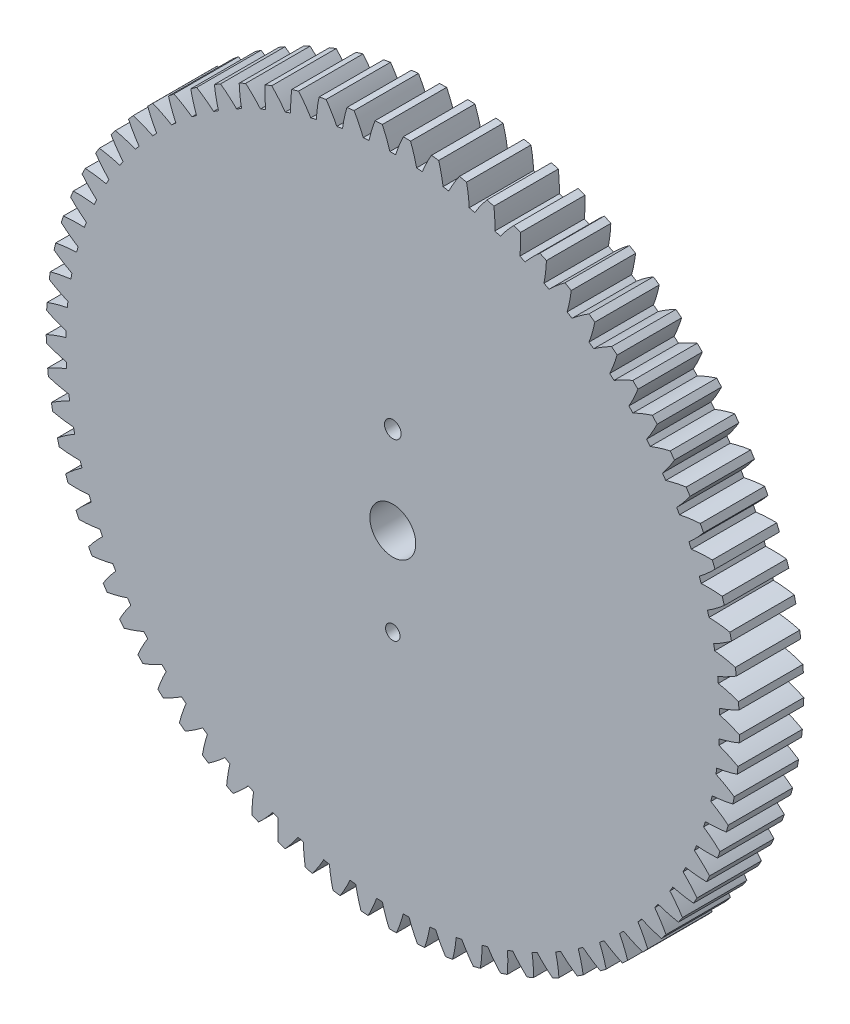
SolidWorks part; units mm, degrees
ref_plane "Front Plane" through (0, 0, 0) normal (0, 0, 1) x (1, 0, 0)
ref_plane "Top Plane" through (0, 0, 0) normal (0, 1, 0) x (1, 0, 0)
ref_plane "Right Plane" through (0, 0, 0) normal (1, 0, 0) x (0, 0, -1)
sketch "Model" plane through (0, 0, 0) normal (0, 0, 1) x (1, 0, 0)
  arc A0 (-39.5739, 2.0126) -> (-37.3581, 1.0914) centre (-32.524, 15.8446) ccw
  arc A1 (-37.3581, 1.0914) -> (-37.3715, 0.4333) centre (0, 0) ccw
  arc A2 (-37.3715, 0.4333) -> (-39.623, -0.3968) centre (-33.1432, -14.5048) ccw
  circle A311 centre (0, -10.05) radius 0.825
  circle A312 centre (0, 10.05) radius 0.825
  circle A313 centre (0, 0) radius 2.625
  arc A314 (-39.623, -0.3968) -> (-39.6062, -1.2197) centre (0, 0) ccw
  arc A315 (-39.6062, -1.2197) -> (-37.3227, -1.9572) centre (-33.7072, 13.1409) ccw
  arc A316 (-37.3227, -1.9572) -> (-37.2825, -2.6143) centre (0, 0) ccw
  arc A317 (-37.2825, -2.6143) -> (-39.4588, -3.6251) centre (-31.8506, -17.158) ccw
  arc A318 (-39.4588, -3.6251) -> (-39.375, -4.4439) centre (0, 0) ccw
  arc A319 (-39.375, -4.4439) -> (-37.039, -4.9929) centre (-34.6662, 10.3497) ccw
  arc A320 (-37.039, -4.9929) -> (-36.9453, -5.6445) centre (0, 0) ccw
  arc A321 (-36.9453, -5.6445) -> (-39.0321, -6.8293) centre (-30.3461, -19.6971) ccw
  arc A322 (-39.0321, -6.8293) -> (-38.8818, -7.6386) centre (0, 0) ccw
  arc A323 (-38.8818, -7.6386) -> (-36.5088, -7.9953) centre (-35.3944, 7.4897) ccw
  arc A324 (-36.5088, -7.9953) -> (-36.3623, -8.6371) centre (0, 0) ccw
  arc A325 (-36.3623, -8.6371) -> (-38.3455, -9.988) centre (-28.6396, -22.105) ccw
  arc A326 (-38.3455, -9.988) -> (-38.1298, -10.7824) centre (0, 0) ccw
  arc A327 (-38.1298, -10.7824) -> (-35.7356, -10.9445) centre (-35.8871, 4.5798) ccw
  arc A328 (-35.7356, -10.9445) -> (-35.5373, -11.5722) centre (0, 0) ccw
  arc A329 (-35.5373, -11.5722) -> (-37.4038, -13.0803) centre (-26.7426, -24.3659) ccw
  arc A330 (-37.4038, -13.0803) -> (-37.124, -13.8544) centre (0, 0) ccw
  arc A331 (-37.124, -13.8544) -> (-34.7246, -13.8209) centre (-36.141, 1.6394) ccw
  arc A332 (-34.7246, -13.8209) -> (-34.4758, -14.4303) centre (0, 0) ccw
  arc A333 (-34.4758, -14.4303) -> (-36.2132, -16.0856) centre (-24.6675, -26.4646) ccw
  arc A334 (-36.2132, -16.0856) -> (-35.8713, -16.8343) centre (0, 0) ccw
  arc A335 (-35.8713, -16.8343) -> (-33.4826, -16.6052) centre (-36.1544, -1.3119) ccw
  arc A336 (-33.4826, -16.6052) -> (-33.1849, -17.1924) centre (0, 0) ccw
  arc A337 (-33.1849, -17.1924) -> (-34.7816, -18.9838) centre (-22.4283, -28.3871) ccw
  arc A338 (-34.7816, -18.9838) -> (-34.3797, -19.7021) centre (0, 0) ccw
  arc A339 (-34.3797, -19.7021) -> (-32.0177, -19.2791) centre (-35.9271, -4.2544) ccw
  arc A340 (-32.0177, -19.2791) -> (-31.6731, -19.8401) centre (0, 0) ccw
  arc A341 (-31.6731, -19.8401) -> (-33.1185, -21.7556) centre (-20.0399, -30.1208) ccw
  arc A342 (-33.1185, -21.7556) -> (-32.6594, -22.4388) centre (0, 0) ccw
  arc A343 (-32.6594, -22.4388) -> (-30.3397, -21.8247) centre (-35.4608, -7.1687) ccw
  arc A344 (-30.3397, -21.8247) -> (-29.9506, -22.3557) centre (0, 0) ccw
  arc A345 (-29.9506, -22.3557) -> (-31.235, -24.3827) centre (-17.5181, -31.654) ccw
  arc A346 (-31.235, -24.3827) -> (-30.7218, -25.0262) centre (0, 0) ccw
  arc A347 (-30.7218, -25.0262) -> (-28.4598, -24.2251) centre (-34.7585, -10.0352) ccw
  arc A348 (-28.4598, -24.2251) -> (-28.0287, -24.7226) centre (0, 0) ccw
  arc A349 (-28.0287, -24.7226) -> (-29.1437, -26.8475) centre (-14.8797, -32.9766) ccw
  arc A350 (-29.1437, -26.8475) -> (-28.5797, -27.4471) centre (0, 0) ccw
  arc A351 (-28.5797, -27.4471) -> (-26.3906, -26.4642) centre (-33.8249, -12.835) ccw
  arc A352 (-26.3906, -26.4642) -> (-25.9204, -26.9249) centre (0, 0) ccw
  arc A353 (-25.9204, -26.9249) -> (-26.8584, -29.1336) centre (-12.1423, -34.0797) ccw
  arc A354 (-26.8584, -29.1336) -> (-26.2474, -29.6852) centre (0, 0) ccw
  arc A355 (-26.2474, -29.6852) -> (-24.1457, -28.5272) centre (-32.6662, -15.5493) ccw
  arc A356 (-24.1457, -28.5272) -> (-23.6395, -28.9481) centre (0, 0) ccw
  arc A357 (-23.6395, -28.9481) -> (-24.3943, -31.2259) centre (-9.3241, -34.956) ccw
  arc A358 (-24.3943, -31.2259) -> (-23.7405, -31.7259) centre (0, 0) ccw
  arc A359 (-23.7405, -31.7259) -> (-21.7401, -30.4004) centre (-31.2901, -18.1602) ccw
  arc A360 (-21.7401, -30.4004) -> (-21.2013, -30.7786) centre (0, 0) ccw
  arc A361 (-21.2013, -30.7786) -> (-21.768, -33.1104) centre (-6.4438, -35.5997) ccw
  arc A362 (-21.768, -33.1104) -> (-21.0755, -33.5554) centre (0, 0) ccw
  arc A363 (-21.0755, -33.5554) -> (-19.1898, -32.0713) centre (-29.7057, -20.6502) ccw
  arc A364 (-19.1898, -32.0713) -> (-18.622, -32.4043) centre (0, 0) ccw
  arc A365 (-18.622, -32.4043) -> (-18.9967, -34.7745) centre (-3.5207, -36.0065) ccw
  arc A366 (-18.9967, -34.7745) -> (-18.2703, -35.1616) centre (0, 0) ccw
  arc A367 (-18.2703, -35.1616) -> (-16.5119, -33.5287) centre (-27.9237, -23.0027) ccw
  arc A368 (-16.5119, -33.5287) -> (-15.9188, -33.8143) centre (0, 0) ccw
  arc A369 (-15.9188, -33.8143) -> (-16.0991, -36.2072) centre (-0.5741, -36.1736) ccw
  arc A370 (-16.0991, -36.2072) -> (-15.3435, -36.5338) centre (0, 0) ccw
  arc A371 (-15.3435, -36.5338) -> (-13.724, -34.763) centre (-25.9559, -25.2022) ccw
  arc A372 (-13.724, -34.763) -> (-13.1096, -34.9993) centre (0, 0) ccw
  arc A373 (-13.1096, -34.9993) -> (-13.0943, -37.3989) centre (2.3763, -36.1) ccw
  arc A374 (-13.0943, -37.3989) -> (-12.3146, -37.6629) centre (0, 0) ccw
  arc A375 (-12.3146, -37.6629) -> (-10.8449, -35.766) centre (-23.8153, -27.234) ccw
  arc A376 (-10.8449, -35.766) -> (-10.2133, -35.9514) centre (0, 0) ccw
  arc A377 (-10.2133, -35.9514) -> (-10.0024, -38.3418) centre (5.3109, -35.7862) ccw
  arc A378 (-10.0024, -38.3418) -> (-9.2038, -38.5413) centre (0, 0) ccw
  arc A379 (-9.2038, -38.5413) -> (-7.8935, -36.5309) centre (-21.5162, -29.0846) ccw
  arc A380 (-7.8935, -36.5309) -> (-7.2489, -36.6643) centre (0, 0) ccw
  arc A381 (-7.2489, -36.6643) -> (-6.8439, -39.0295) centre (8.2101, -35.2343) ccw
  arc A382 (-6.8439, -39.0295) -> (-6.0317, -39.1632) centre (0, 0) ccw
  arc A383 (-6.0317, -39.1632) -> (-4.8897, -37.0528) centre (-19.074, -30.7416) ccw
  arc A384 (-4.8897, -37.0528) -> (-4.2363, -37.1331) centre (0, 0) ccw
  arc A385 (-4.2363, -37.1331) -> (-3.6398, -39.4575) centre (11.0547, -34.4478) ccw
  arc A386 (-3.6398, -39.4575) -> (-2.8194, -39.5246) centre (0, 0) ccw
  arc A387 (-2.8194, -39.5246) -> (-1.8532, -37.328) centre (-16.5048, -32.194) ccw
  arc A388 (-1.8532, -37.328) -> (-1.1955, -37.3549) centre (0, 0) ccw
  arc A389 (-1.1955, -37.3549) -> (-0.4116, -39.6229) centre (13.8257, -33.4321) ccw
  arc A390 (-0.4116, -39.6229) -> (0.4116, -39.6229) centre (0, 0) ccw
  arc A391 (0.4116, -39.6229) -> (1.1955, -37.3549) centre (-13.8257, -33.4321) ccw
  arc A392 (1.1955, -37.3549) -> (1.8532, -37.328) centre (0, 0) ccw
  arc A393 (1.8532, -37.328) -> (2.8194, -39.5246) centre (16.5048, -32.194) ccw
  arc A394 (2.8194, -39.5246) -> (3.6398, -39.4575) centre (0, 0) ccw
  arc A395 (3.6398, -39.4575) -> (4.2363, -37.1331) centre (-11.0547, -34.4478) ccw
  arc A396 (4.2363, -37.1331) -> (4.8897, -37.0528) centre (0, 0) ccw
  arc A397 (4.8897, -37.0528) -> (6.0317, -39.1632) centre (19.074, -30.7416) ccw
  arc A398 (6.0317, -39.1632) -> (6.8439, -39.0295) centre (0, 0) ccw
  arc A399 (6.8439, -39.0295) -> (7.2489, -36.6643) centre (-8.2101, -35.2343) ccw
  arc A400 (7.2489, -36.6643) -> (7.8935, -36.5309) centre (0, 0) ccw
  arc A401 (7.8935, -36.5309) -> (9.2038, -38.5413) centre (21.5162, -29.0846) ccw
  arc A402 (9.2038, -38.5413) -> (10.0024, -38.3418) centre (0, 0) ccw
  arc A403 (10.0024, -38.3418) -> (10.2133, -35.9514) centre (-5.3109, -35.7862) ccw
  arc A404 (10.2133, -35.9514) -> (10.8449, -35.766) centre (0, 0) ccw
  arc A405 (10.8449, -35.766) -> (12.3146, -37.6629) centre (23.8153, -27.234) ccw
  arc A406 (12.3146, -37.6629) -> (13.0943, -37.3989) centre (0, 0) ccw
  arc A407 (13.0943, -37.3989) -> (13.1096, -34.9993) centre (-2.3763, -36.1) ccw
  arc A408 (13.1096, -34.9993) -> (13.724, -34.763) centre (0, 0) ccw
  arc A409 (13.724, -34.763) -> (15.3435, -36.5338) centre (25.9559, -25.2022) ccw
  arc A410 (15.3435, -36.5338) -> (16.0991, -36.2072) centre (0, 0) ccw
  arc A411 (16.0991, -36.2072) -> (15.9188, -33.8143) centre (0.5741, -36.1736) ccw
  arc A412 (15.9188, -33.8143) -> (16.5119, -33.5287) centre (0, 0) ccw
  arc A413 (16.5119, -33.5287) -> (18.2703, -35.1616) centre (27.9237, -23.0027) ccw
  arc A414 (18.2703, -35.1616) -> (18.9967, -34.7745) centre (0, 0) ccw
  arc A415 (18.9967, -34.7745) -> (18.622, -32.4043) centre (3.5207, -36.0065) ccw
  arc A416 (18.622, -32.4043) -> (19.1898, -32.0713) centre (0, 0) ccw
  arc A417 (19.1898, -32.0713) -> (21.0755, -33.5554) centre (29.7057, -20.6502) ccw
  arc A418 (21.0755, -33.5554) -> (21.768, -33.1104) centre (0, 0) ccw
  arc A419 (21.768, -33.1104) -> (21.2013, -30.7786) centre (6.4438, -35.5997) ccw
  arc A420 (21.2013, -30.7786) -> (21.7401, -30.4004) centre (0, 0) ccw
  arc A421 (21.7401, -30.4004) -> (23.7405, -31.7259) centre (31.2901, -18.1602) ccw
  arc A422 (23.7405, -31.7259) -> (24.3943, -31.2259) centre (0, 0) ccw
  arc A423 (24.3943, -31.2259) -> (23.6395, -28.9481) centre (9.3241, -34.956) ccw
  arc A424 (23.6395, -28.9481) -> (24.1457, -28.5272) centre (0, 0) ccw
  arc A425 (24.1457, -28.5272) -> (26.2474, -29.6852) centre (32.6662, -15.5493) ccw
  arc A426 (26.2474, -29.6852) -> (26.8584, -29.1336) centre (0, 0) ccw
  arc A427 (26.8584, -29.1336) -> (25.9204, -26.9249) centre (12.1423, -34.0797) ccw
  arc A428 (25.9204, -26.9249) -> (26.3906, -26.4642) centre (0, 0) ccw
  arc A429 (26.3906, -26.4642) -> (28.5797, -27.4471) centre (33.8249, -12.835) ccw
  arc A430 (28.5797, -27.4471) -> (29.1437, -26.8475) centre (0, 0) ccw
  arc A431 (29.1437, -26.8475) -> (28.0287, -24.7226) centre (14.8797, -32.9766) ccw
  arc A432 (28.0287, -24.7226) -> (28.4598, -24.2251) centre (0, 0) ccw
  arc A433 (28.4598, -24.2251) -> (30.7218, -25.0262) centre (34.7585, -10.0352) ccw
  arc A434 (30.7218, -25.0262) -> (31.235, -24.3827) centre (0, 0) ccw
  arc A435 (31.235, -24.3827) -> (29.9506, -22.3557) centre (17.5181, -31.654) ccw
  arc A436 (29.9506, -22.3557) -> (30.3397, -21.8247) centre (0, 0) ccw
  arc A437 (30.3397, -21.8247) -> (32.6594, -22.4388) centre (35.4608, -7.1687) ccw
  arc A438 (32.6594, -22.4388) -> (33.1185, -21.7556) centre (0, 0) ccw
  arc A439 (33.1185, -21.7556) -> (31.6731, -19.8401) centre (20.0399, -30.1208) ccw
  arc A440 (31.6731, -19.8401) -> (32.0177, -19.2791) centre (0, 0) ccw
  arc A441 (32.0177, -19.2791) -> (34.3797, -19.7021) centre (35.9271, -4.2544) ccw
  arc A442 (34.3797, -19.7021) -> (34.7816, -18.9838) centre (0, 0) ccw
  arc A443 (34.7816, -18.9838) -> (33.1849, -17.1924) centre (22.4283, -28.3871) ccw
  arc A444 (33.1849, -17.1924) -> (33.4826, -16.6052) centre (0, 0) ccw
  arc A445 (33.4826, -16.6052) -> (35.8713, -16.8343) centre (36.1544, -1.3119) ccw
  arc A446 (35.8713, -16.8343) -> (36.2132, -16.0856) centre (0, 0) ccw
  arc A447 (36.2132, -16.0856) -> (34.4758, -14.4303) centre (24.6675, -26.4646) ccw
  arc A448 (34.4758, -14.4303) -> (34.7246, -13.8209) centre (0, 0) ccw
  arc A449 (34.7246, -13.8209) -> (37.124, -13.8544) centre (36.141, 1.6394) ccw
  arc A450 (37.124, -13.8544) -> (37.4038, -13.0803) centre (0, 0) ccw
  arc A451 (37.4038, -13.0803) -> (35.5373, -11.5722) centre (26.7426, -24.3659) ccw
  arc A452 (35.5373, -11.5722) -> (35.7356, -10.9445) centre (0, 0) ccw
  arc A453 (35.7356, -10.9445) -> (38.1298, -10.7824) centre (35.8871, 4.5798) ccw
  arc A454 (38.1298, -10.7824) -> (38.3455, -9.988) centre (0, 0) ccw
  arc A455 (38.3455, -9.988) -> (36.3623, -8.6371) centre (28.6396, -22.105) ccw
  arc A456 (36.3623, -8.6371) -> (36.5088, -7.9953) centre (0, 0) ccw
  arc A457 (36.5088, -7.9953) -> (38.8818, -7.6386) centre (35.3944, 7.4897) ccw
  arc A458 (38.8818, -7.6386) -> (39.0321, -6.8293) centre (0, 0) ccw
  arc A459 (39.0321, -6.8293) -> (36.9453, -5.6445) centre (30.3461, -19.6971) ccw
  arc A460 (36.9453, -5.6445) -> (37.039, -4.9929) centre (0, 0) ccw
  arc A461 (37.039, -4.9929) -> (39.375, -4.4439) centre (34.6662, 10.3497) ccw
  arc A462 (39.375, -4.4439) -> (39.4588, -3.6251) centre (0, 0) ccw
  arc A463 (39.4588, -3.6251) -> (37.2825, -2.6143) centre (31.8506, -17.158) ccw
  arc A464 (37.2825, -2.6143) -> (37.3227, -1.9572) centre (0, 0) ccw
  arc A465 (37.3227, -1.9572) -> (39.6062, -1.2197) centre (33.7072, 13.1409) ccw
  arc A466 (39.6062, -1.2197) -> (39.623, -0.3968) centre (0, 0) ccw
  arc A467 (39.623, -0.3968) -> (37.3715, 0.4333) centre (33.1432, -14.5048) ccw
  arc A468 (37.3715, 0.4333) -> (37.3581, 1.0914) centre (0, 0) ccw
  arc A469 (37.3581, 1.0914) -> (39.5739, 2.0126) centre (32.524, 15.8446) ccw
  arc A470 (39.5739, 2.0126) -> (39.5235, 2.8342) centre (0, 0) ccw
  arc A471 (39.5235, 2.8342) -> (37.2118, 3.478) centre (34.2152, -11.7551) ccw
  arc A472 (37.2118, 3.478) -> (37.1448, 4.1328) centre (0, 0) ccw
  arc A473 (37.1448, 4.1328) -> (39.2781, 5.2315) centre (31.1243, 18.4429) ccw
  arc A474 (39.2781, 5.2315) -> (39.161, 6.0463) centre (0, 0) ccw
  arc A475 (39.161, 6.0463) -> (36.8045, 6.4995) centre (35.0595, -8.9271) ccw
  arc A476 (36.8045, 6.4995) -> (36.6843, 7.1467) centre (0, 0) ccw
  arc A477 (36.6843, 7.1467) -> (38.721, 8.4157) centre (29.5174, 20.9185) ccw
  arc A478 (38.721, 8.4157) -> (38.5379, 9.2182) centre (0, 0) ccw
  arc A479 (38.5379, 9.2182) -> (36.1523, 9.4778) centre (35.6705, -6.0397) ccw
  arc A480 (36.1523, 9.4778) -> (35.9797, 10.113) centre (0, 0) ccw
  arc A481 (35.9797, 10.113) -> (37.9062, 11.5438) centre (27.7142, 23.2548) ccw
  arc A482 (37.9062, 11.5438) -> (37.6583, 12.3287) centre (0, 0) ccw
  arc A483 (37.6583, 12.3287) -> (35.2595, 12.393) centre (36.0441, -3.1122) ccw
  arc A484 (35.2595, 12.393) -> (35.0357, 13.0121) centre (0, 0) ccw
  arc A485 (35.0357, 13.0121) -> (36.8392, 14.5951) centre (25.7265, 25.4364) ccw
  arc A486 (36.8392, 14.5951) -> (36.5281, 15.3572) centre (0, 0) ccw
  arc A487 (36.5281, 15.3572) -> (34.132, 15.2257) centre (36.1778, -0.1639) ccw
  arc A488 (34.132, 15.2257) -> (33.8585, 15.8245) centre (0, 0) ccw
  arc A489 (33.8585, 15.8245) -> (35.5269, 17.5493) centre (23.5676, 27.4487) ccw
  arc A490 (35.5269, 17.5493) -> (35.1548, 18.2834) centre (0, 0) ccw
  arc A491 (35.1548, 18.2834) -> (32.7774, 17.9571) centre (36.0708, 2.7855) ccw
  arc A492 (32.7774, 17.9571) -> (32.456, 18.5316) centre (0, 0) ccw
  arc A493 (32.456, 18.5316) -> (33.9783, 20.3866) centre (21.2518, 29.2783) ccw
  arc A494 (33.9783, 20.3866) -> (33.5475, 21.088) centre (0, 0) ccw
  arc A495 (33.5475, 21.088) -> (31.2047, 20.569) centre (35.7237, 5.7163) ccw
  arc A496 (31.2047, 20.569) -> (30.8375, 21.1154) centre (0, 0) ccw
  arc A497 (30.8375, 21.1154) -> (32.2035, 23.0884) centre (18.7946, 30.9131) ccw
  arc A498 (32.2035, 23.0884) -> (31.717, 23.7523) centre (0, 0) ccw
  arc A499 (31.717, 23.7523) -> (29.4243, 23.0441) centre (35.1389, 8.6091) ccw
  arc A500 (29.4243, 23.0441) -> (29.0138, 23.5587) centre (0, 0) ccw
  arc A501 (29.0138, 23.5587) -> (30.2145, 25.6364) centre (16.2124, 32.3422) ccw
  arc A502 (30.2145, 25.6364) -> (29.6754, 26.2585) centre (0, 0) ccw
  arc A503 (29.6754, 26.2585) -> (27.448, 25.3657) centre (34.3203, 11.4446) ccw
  arc A504 (27.448, 25.3657) -> (26.997, 25.8452) centre (0, 0) ccw
  arc A505 (26.997, 25.8452) -> (28.0243, 28.0139) centre (13.5223, 33.556) ccw
  arc A506 (28.0243, 28.0139) -> (27.4364, 28.5899) centre (0, 0) ccw
  arc A507 (27.4364, 28.5899) -> (25.2892, 27.5186) centre (33.2732, 14.2039) ccw
  arc A508 (25.2892, 27.5186) -> (24.8006, 27.9598) centre (0, 0) ccw
  arc A509 (24.8006, 27.9598) -> (25.6477, 30.2049) centre (10.7421, 34.5466) ccw
  arc A510 (25.6477, 30.2049) -> (25.0148, 30.7311) centre (0, 0) ccw
  arc A511 (25.0148, 30.7311) -> (22.962, 29.4883) centre (32.0048, 16.8688) ccw
  arc A512 (22.962, 29.4883) -> (22.4391, 29.8882) centre (0, 0) ccw
  arc A513 (22.4391, 29.8882) -> (23.1004, 32.1949) centre (7.8905, 35.3072) ccw
  arc A514 (23.1004, 32.1949) -> (22.4266, 32.6678) centre (0, 0) ccw
  arc A515 (22.4266, 32.6678) -> (20.482, 31.2618) centre (30.5233, 19.4213) ccw
  arc A516 (20.482, 31.2618) -> (19.9282, 31.6177) centre (0, 0) ccw
  arc A517 (19.9282, 31.6177) -> (20.3993, 33.9707) centre (4.9864, 35.8329) ccw
  arc A518 (20.3993, 33.9707) -> (19.6893, 34.3871) centre (0, 0) ccw
  arc A519 (19.6893, 34.3871) -> (17.8657, 32.8273) centre (28.8387, 21.8446) ccw
  arc A520 (17.8657, 32.8273) -> (17.2848, 33.1369) centre (0, 0) ccw
  arc A521 (17.2848, 33.1369) -> (17.5625, 35.5204) centre (2.0491, 36.1201) ccw
  arc A522 (17.5625, 35.5204) -> (16.8209, 35.8775) centre (0, 0) ccw
  arc A523 (16.8209, 35.8775) -> (15.1306, 34.1743) centre (26.9622, 24.1226) ccw
  arc A524 (15.1306, 34.1743) -> (14.5263, 34.4355) centre (0, 0) ccw
  arc A525 (14.5263, 34.4355) -> (14.6088, 36.8337) centre (-0.9018, 36.1669) ccw
  arc A526 (14.6088, 36.8337) -> (13.8406, 37.1292) centre (0, 0) ccw
  arc A527 (13.8406, 37.1292) -> (12.2947, 35.2939) centre (24.9063, 26.24) ccw
  arc A528 (12.2947, 35.2939) -> (11.6712, 35.5049) centre (0, 0) ccw
  arc A529 (11.6712, 35.5049) -> (11.5579, 37.9019) centre (-3.8468, 35.9731) ccw
  arc A530 (11.5579, 37.9019) -> (10.7682, 38.1338) centre (0, 0) ccw
  arc A531 (10.7682, 38.1338) -> (9.377, 36.1786) centre (22.6846, 28.1828) ccw
  arc A532 (9.377, 36.1786) -> (8.7384, 36.3381) centre (0, 0) ccw
  arc A533 (8.7384, 36.3381) -> (8.4301, 38.7179) centre (-6.7661, 35.5398) ccw
  arc A534 (8.4301, 38.7179) -> (7.6241, 38.8846) centre (0, 0) ccw
  arc A535 (7.6241, 38.8846) -> (6.3969, 36.8225) centre (20.312, 29.938) ccw
  arc A536 (6.3969, 36.8225) -> (5.7474, 36.9294) centre (0, 0) ccw
  arc A537 (5.7474, 36.9294) -> (5.2462, 39.2762) centre (-9.6404, 34.8701) ccw
  arc A538 (5.2462, 39.2762) -> (4.4292, 39.3767) centre (0, 0) ccw
  arc A539 (4.4292, 39.3767) -> (3.3743, 37.2214) centre (17.8042, 31.494) ccw
  arc A540 (3.3743, 37.2214) -> (2.7182, 37.275) centre (0, 0) ccw
  arc A541 (2.7182, 37.275) -> (2.0274, 39.5731) centre (-12.4506, 33.9683) ccw
  arc A542 (2.0274, 39.5731) -> (1.2049, 39.6067) centre (0, 0) ccw
  arc A543 (1.2049, 39.6067) -> (0.3291, 37.3726) centre (15.1779, 32.8404) ccw
  arc A544 (0.3291, 37.3726) -> (-0.3291, 37.3726) centre (0, 0) ccw
  arc A545 (-0.3291, 37.3726) -> (-1.2049, 39.6067) centre (-15.1779, 32.8404) ccw
  arc A546 (-1.2049, 39.6067) -> (-2.0274, 39.5731) centre (0, 0) ccw
  arc A547 (-2.0274, 39.5731) -> (-2.7182, 37.275) centre (12.4506, 33.9683) ccw
  arc A548 (-2.7182, 37.275) -> (-3.3743, 37.2214) centre (0, 0) ccw
  arc A549 (-3.3743, 37.2214) -> (-4.4292, 39.3767) centre (-17.8042, 31.494) ccw
  arc A550 (-4.4292, 39.3767) -> (-5.2462, 39.2762) centre (0, 0) ccw
  arc A551 (-5.2462, 39.2762) -> (-5.7474, 36.9294) centre (9.6404, 34.8701) ccw
  arc A552 (-5.7474, 36.9294) -> (-6.3969, 36.8225) centre (0, 0) ccw
  arc A553 (-6.3969, 36.8225) -> (-7.6241, 38.8846) centre (-20.312, 29.938) ccw
  arc A554 (-7.6241, 38.8846) -> (-8.4301, 38.7179) centre (0, 0) ccw
  arc A555 (-8.4301, 38.7179) -> (-8.7384, 36.3381) centre (6.7661, 35.5398) ccw
  arc A556 (-8.7384, 36.3381) -> (-9.377, 36.1786) centre (0, 0) ccw
  arc A557 (-9.377, 36.1786) -> (-10.7682, 38.1338) centre (-22.6846, 28.1828) ccw
  arc A558 (-10.7682, 38.1338) -> (-11.5579, 37.9019) centre (0, 0) ccw
  arc A559 (-11.5579, 37.9019) -> (-11.6712, 35.5049) centre (3.8468, 35.9731) ccw
  arc A560 (-11.6712, 35.5049) -> (-12.2947, 35.2939) centre (0, 0) ccw
  arc A561 (-12.2947, 35.2939) -> (-13.8406, 37.1292) centre (-24.9063, 26.24) ccw
  arc A562 (-13.8406, 37.1292) -> (-14.6088, 36.8337) centre (0, 0) ccw
  arc A563 (-14.6088, 36.8337) -> (-14.5263, 34.4355) centre (0.9018, 36.1669) ccw
  arc A564 (-14.5263, 34.4355) -> (-15.1306, 34.1743) centre (0, 0) ccw
  arc A565 (-15.1306, 34.1743) -> (-16.8209, 35.8775) centre (-26.9622, 24.1226) ccw
  arc A566 (-16.8209, 35.8775) -> (-17.5625, 35.5204) centre (0, 0) ccw
  arc A567 (-17.5625, 35.5204) -> (-17.2848, 33.1369) centre (-2.0491, 36.1201) ccw
  arc A568 (-17.2848, 33.1369) -> (-17.8657, 32.8273) centre (0, 0) ccw
  arc A569 (-17.8657, 32.8273) -> (-19.6893, 34.3871) centre (-28.8387, 21.8446) ccw
  arc A570 (-19.6893, 34.3871) -> (-20.3993, 33.9707) centre (0, 0) ccw
  arc A571 (-20.3993, 33.9707) -> (-19.9282, 31.6177) centre (-4.9864, 35.8329) ccw
  arc A572 (-19.9282, 31.6177) -> (-20.482, 31.2618) centre (0, 0) ccw
  arc A573 (-20.482, 31.2618) -> (-22.4266, 32.6678) centre (-30.5233, 19.4213) ccw
  arc A574 (-22.4266, 32.6678) -> (-23.1004, 32.1949) centre (0, 0) ccw
  arc A575 (-23.1004, 32.1949) -> (-22.4391, 29.8882) centre (-7.8905, 35.3072) ccw
  arc A576 (-22.4391, 29.8882) -> (-22.962, 29.4883) centre (0, 0) ccw
  arc A577 (-22.962, 29.4883) -> (-25.0148, 30.7311) centre (-32.0048, 16.8688) ccw
  arc A578 (-25.0148, 30.7311) -> (-25.6477, 30.2049) centre (0, 0) ccw
  arc A579 (-25.6477, 30.2049) -> (-24.8006, 27.9598) centre (-10.7421, 34.5466) ccw
  arc A580 (-24.8006, 27.9598) -> (-25.2892, 27.5186) centre (0, 0) ccw
  arc A581 (-25.2892, 27.5186) -> (-27.4364, 28.5899) centre (-33.2732, 14.2039) ccw
  arc A582 (-27.4364, 28.5899) -> (-28.0243, 28.0139) centre (0, 0) ccw
  arc A583 (-28.0243, 28.0139) -> (-26.997, 25.8452) centre (-13.5223, 33.556) ccw
  arc A584 (-26.997, 25.8452) -> (-27.448, 25.3657) centre (0, 0) ccw
  arc A585 (-27.448, 25.3657) -> (-29.6754, 26.2585) centre (-34.3203, 11.4446) ccw
  arc A586 (-29.6754, 26.2585) -> (-30.2145, 25.6364) centre (0, 0) ccw
  arc A587 (-30.2145, 25.6364) -> (-29.0138, 23.5587) centre (-16.2124, 32.3422) ccw
  arc A588 (-29.0138, 23.5587) -> (-29.4243, 23.0441) centre (0, 0) ccw
  arc A589 (-29.4243, 23.0441) -> (-31.717, 23.7523) centre (-35.1389, 8.6091) ccw
  arc A590 (-31.717, 23.7523) -> (-32.2035, 23.0884) centre (0, 0) ccw
  arc A591 (-32.2035, 23.0884) -> (-30.8375, 21.1154) centre (-18.7946, 30.9131) ccw
  arc A592 (-30.8375, 21.1154) -> (-31.2047, 20.569) centre (0, 0) ccw
  arc A593 (-31.2047, 20.569) -> (-33.5475, 21.088) centre (-35.7237, 5.7163) ccw
  arc A594 (-33.5475, 21.088) -> (-33.9783, 20.3866) centre (0, 0) ccw
  arc A595 (-33.9783, 20.3866) -> (-32.456, 18.5316) centre (-21.2518, 29.2783) ccw
  arc A596 (-32.456, 18.5316) -> (-32.7774, 17.9571) centre (0, 0) ccw
  arc A597 (-32.7774, 17.9571) -> (-35.1548, 18.2834) centre (-36.0708, 2.7855) ccw
  arc A598 (-35.1548, 18.2834) -> (-35.5269, 17.5493) centre (0, 0) ccw
  arc A599 (-35.5269, 17.5493) -> (-33.8585, 15.8245) centre (-23.5676, 27.4487) ccw
  arc A600 (-33.8585, 15.8245) -> (-34.132, 15.2257) centre (0, 0) ccw
  arc A601 (-34.132, 15.2257) -> (-36.5281, 15.3572) centre (-36.1778, -0.1639) ccw
  arc A602 (-36.5281, 15.3572) -> (-36.8392, 14.5951) centre (0, 0) ccw
  arc A603 (-36.8392, 14.5951) -> (-35.0357, 13.0121) centre (-25.7265, 25.4364) ccw
  arc A604 (-35.0357, 13.0121) -> (-35.2595, 12.393) centre (0, 0) ccw
  arc A605 (-35.2595, 12.393) -> (-37.6583, 12.3287) centre (-36.0441, -3.1122) ccw
  arc A606 (-37.6583, 12.3287) -> (-37.9062, 11.5438) centre (0, 0) ccw
  arc A607 (-37.9062, 11.5438) -> (-35.9797, 10.113) centre (-27.7142, 23.2548) ccw
  arc A608 (-35.9797, 10.113) -> (-36.1523, 9.4778) centre (0, 0) ccw
  arc A609 (-36.1523, 9.4778) -> (-38.5379, 9.2182) centre (-35.6705, -6.0397) ccw
  arc A610 (-38.5379, 9.2182) -> (-38.721, 8.4157) centre (0, 0) ccw
  arc A611 (-38.721, 8.4157) -> (-36.6843, 7.1467) centre (-29.5174, 20.9185) ccw
  arc A612 (-36.6843, 7.1467) -> (-36.8045, 6.4995) centre (0, 0) ccw
  arc A613 (-36.8045, 6.4995) -> (-39.161, 6.0463) centre (-35.0595, -8.9271) ccw
  arc A614 (-39.161, 6.0463) -> (-39.2781, 5.2315) centre (0, 0) ccw
  arc A615 (-39.2781, 5.2315) -> (-37.1448, 4.1328) centre (-31.1243, 18.4429) ccw
  arc A616 (-37.1448, 4.1328) -> (-37.2118, 3.478) centre (0, 0) ccw
  arc A617 (-37.2118, 3.478) -> (-39.5235, 2.8342) centre (-34.2152, -11.7551) ccw
  arc A618 (-39.5235, 2.8342) -> (-39.5739, 2.0126) centre (0, 0) ccw
  circle A619 centre (0, 10.05) radius 0.95
  dimension "D1" = 0.125
extrude "Boss-Extrude1" add sketch "Model" along normal blind 7.3641 contours A617 A618 A0 A1 A2 A314 A315 A316 A317 A318 A319 A320 A321 A322 A323 A324 A325 A326 A327 A328 A329 A330 A331 A332 A333 A334 A335 A336 A337 A338 A339 A340 A341 A342 A343 A344 A345 A346 A347 A348 A349 A350 A351 A352 A353 A354 A355 A356 A357 A358 A359 region at (-38.4323, 2.355, 0)
